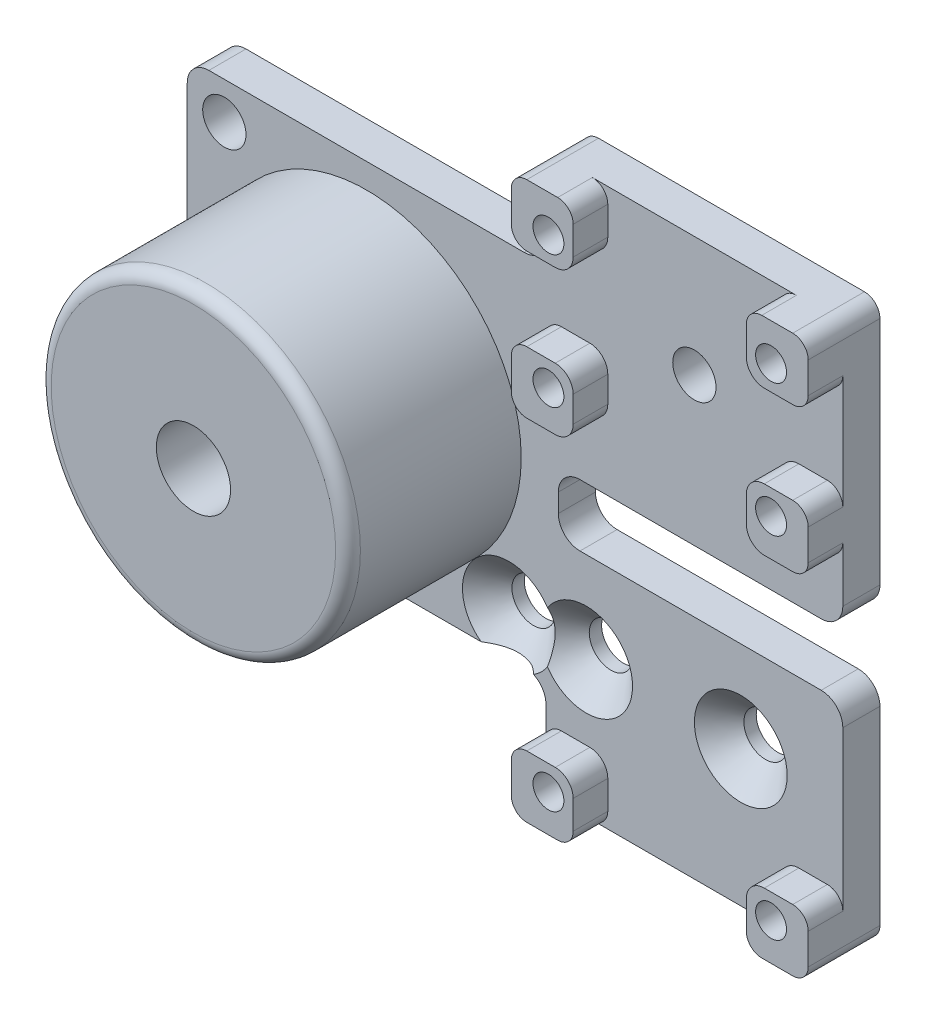
SolidWorks part; units mm, degrees
note: The reader was unsure of these and kept them because the rebuilt part matched: shared geometry of "Esquisse1<3>", "Esquisse1<5>", "Esquisse4<3>".
ref_plane "Plan de face" through (0, 0, 0) normal (0, 0, 1) x (1, 0, 0)
ref_plane "Plan de dessus" through (0, 0, 0) normal (0, 1, 0) x (1, 0, 0)
ref_plane "Plan de droite" through (0, 0, 0) normal (1, 0, 0) x (0, 0, -1)
sketch "Esquisse1" plane through (0, 0, 0) normal (0, 0, 1) x (1, 0, 0)
  line L1 (11.5, -11.5) -> (-11.5, -11.5) construction
  line L2 (11.5, -11.5) -> (11.5, 11.5) construction
  line L3 (11.5, 11.5) -> (-11.5, 11.5) construction
  line L4 (-11.5, -11.5) -> (-11.5, 11.5) construction
  line L5 (11.5, -11.5) -> (-11.5, 11.5) construction
  line L6 (11.5, 11.5) -> (-11.5, -11.5) construction
  line L13 (0, 14.5) -> (-14.5, 14.5)
  line L14 (14.5, -14.5) -> (-14.5, -14.5) construction
  line L15 (14.5, -14.5) -> (14.5, 14.5) construction
  line L16 (14.5, 14.5) -> (-14.5, 14.5) construction
  line L17 (-14.5, -14.5) -> (-14.5, 14.5) construction
  line L18 (14.5, -14.5) -> (-14.5, 14.5) construction
  line L19 (14.5, 14.5) -> (-14.5, -14.5) construction
  line L20 (-14.5, 14.5) -> (-14.5, -14.5)
  line L21 (-14.5, -14.5) -> (14.5, -14.5)
  line L22 (14.5, -14.5) -> (14.5, 0)
  circle A0 centre (0, 0) radius 10.5
  circle A2 centre (0, 0) radius 12.5
  circle A4 centre (0, 0) radius 3
  circle A5 centre (-11.5, 11.5) radius 1.75
  circle A6 centre (11.5, -11.5) radius 1.75
  circle A7 centre (-11.5, -11.5) radius 1.75
  arc A8 (0, 14.5) -> (14.5, 0) centre (0, 0) cw
  point P0 (0, 0)
  dimension "D2" = 21
  dimension "D3" = 2
  dimension "D5" = 6
  dimension "D7" = 3.5
  dimension "D1" = 23
  dimension "D6" = 29
extrude "Boss.-Extru.1" add sketch "Esquisse1" along normal blind 3
extrude "Boss.-Extru.2" add sketch "Esquisse1<3>" along normal blind 17
sketch "Esquisse1<3>" plane through (0, 0, 0) normal (0, 0, 1) x (1, 0, 0) same geometry as "Esquisse1"
extrude "Enlèv. mat.-Extru.1" cut sketch "Esquisse1<5>" along normal blind 10
sketch "Esquisse1<5>" plane through (0, 0, 0) normal (0, 0, 1) x (1, 0, 0) same geometry as "Esquisse1"
sketch "Esquisse4" plane through (0, 0, 0) normal (0, 0, -1) x (-1, 0, 0)
  line L0 (-11.5, -11.5) -> (-17.7503, -11.5) construction
  line L14 (-14.5, 22.5) -> (-14.5, -22.5)
  line L15 (-14.5, -14.5) -> (-14.5, 0) construction
  line L18 (-15.5, 0.85) -> (-38.5, 0.85)
  line L31 (-17.7503, -11.5) -> (-30.2503, -11.5) construction
  line L32 (-26.5, 12.8) -> (-26.5, 22.5) construction
  line L33 (-35.5, 8.8) -> (-35.5, 19.5) construction
  line L34 (-35.5, 8.8) -> (-35.5, -19.5) construction
  line L35 (-35.5, 19.5) -> (-38.5, 19.5) construction
  line L36 (-35.5, 19.5) -> (-35.5, 22.5) construction
  line L37 (-35.5, 8.8) -> (-38.5, 5.8) construction
  line L38 (-35.5, 8.8) -> (-33.5, 10.8) construction
  line L39 (-19.5, -22.5) -> (-19.5, -17.5)
  line L40 (-14.5, -17.5) -> (-19.5, -17.5)
  line L41 (-14.5, 5.8) -> (-19.5, 5.8)
  line L42 (-19.5, 10.8) -> (-19.5, 5.8)
  line L43 (-14.5, 10.8) -> (-19.5, 10.8)
  line L44 (-19.5, 22.5) -> (-19.5, 17.5)
  line L45 (-14.5, 17.5) -> (-19.5, 17.5)
  line L46 (0, 14.5) -> (14.5, 14.5) construction
  line L47 (0, 14.5) -> (-14.5, 14.5)
  line L48 (-17.5, 8.8) -> (-35.5, 8.8) construction
  line L49 (-26.5, 12.8) -> (-26.5, 8.8) construction
  line L51 (-33.5, 22.5) -> (-33.5, 17.5)
  line L52 (-38.5, 17.5) -> (-33.5, 17.5)
  line L53 (-33.5, 10.8) -> (-33.5, 5.8)
  line L54 (-38.5, 10.8) -> (-33.5, 10.8)
  line L55 (-38.5, 5.8) -> (-33.5, 5.8)
  line L56 (-38.5, -17.5) -> (-33.5, -17.5)
  line L57 (-33.5, -22.5) -> (-33.5, -17.5)
  line L59 (-38.5, -4.15) -> (-15.5, -4.15)
  line L60 (-15.5, 0.85) -> (-15.5, -4.15)
  line L79 (-38.5, -22.5) -> (-14.5, -22.5)
  line L83 (-38.5, 22.5) -> (-14.5, 22.5)
  line L84 (-38.5, 22.5) -> (-38.5, -22.5)
  circle A8 centre (11.5, 11.5) radius 1.75 construction
  circle A11 centre (-17.7503, -11.5) radius 1.75
  circle A12 centre (-30.2503, -11.5) radius 1.75
  circle A13 centre (-26.5, 12.8) radius 1.75
  circle A14 centre (-35.5, 19.5) radius 1.25
  circle A15 centre (-35.5, 8.8) radius 1.25
  circle A16 centre (-35.5, -19.5) radius 1.25
  circle A17 centre (-17.5, 8.8) radius 1.25
  circle A18 centre (-17.5, -19.5) radius 1.25
  circle A19 centre (-17.5, 19.5) radius 1.25
  arc A20 (-14.5, 0) -> (0, 14.5) centre (0, 0) cw
  arc A21 (0, 14.5) -> (-14.5, 0) centre (0, 0) ccw construction
  point P8 (-38.5, 0)
  dimension "D3" = 5
  dimension "D4" = 5
  dimension "D6" = 18.35
  dimension "D7" = 12.5
  dimension "D8" = 4
  dimension "D10" = 10.7
  dimension "D12" = 2.5
  dimension "D13" = 1
  dimension "D1" = 45
  dimension "D2" = 24
  dimension "D5" = 6.2503
  dimension "D9" = 28.3
  dimension "D11" = 3
extrude "Boss.-Extru.4" add sketch "Esquisse4" against normal up to surface (3 mm away)
extrude "Boss.-Extru.5" add sketch "Esquisse4<3>" against normal blind 5.8 contours L39 L79 L14 L40 A18 | L56 L84 L79 L57 A16 | L54 L84 L55 L53 A15 | L83 L84 L52 L51 A14 | L83 L44 L45 L14 A19 | L14 L43 L42 L41 A17
sketch "Esquisse4<3>" plane through (0, 0, 0) normal (0, 0, -1) x (-1, 0, 0) same geometry as "Esquisse4"
fillet "Congé4" radius 1.75 8 edges at (14.5, -14.5, 1.5) (-14.5, -14.5, 1.5) (-14.5, 14.5, 1.5) (38.5, -4.15, 1.5) (15.5, -4.15, 1.5) (15.5, 0.85, 1.5) (38.5, 0.85, 1.5) (14.5, 14.5, 1.5)
fillet "Congé5" radius 1.25 16 edges at (19.5, -22.5, 4.4) (14.5, -17.5, 4.4) (38.5, -17.5, 4.4) (33.5, -22.5, 4.4) (38.5, 10.8, 4.4) (38.5, 5.8, 4.4) (33.5, 22.5, 4.4) (38.5, 17.5, 4.4) (19.5, 22.5, 4.4) (14.5, 17.5, 4.4) (14.5, 10.8, 4.4) (14.5, 5.8, 4.4) (14.5, -22.5, 2.9) (38.5, -22.5, 2.9) (38.5, 22.5, 2.9) (14.5, 22.5, 2.9)
fillet "Congé6" radius 1.45 8 edges at (19.5, 17.5, 4.4) (33.5, 17.5, 4.4) (33.5, 5.8, 4.4) (33.5, 10.8, 4.4) (19.5, 10.8, 4.4) (19.5, 5.8, 4.4) (19.5, -17.5, 4.4) (33.5, -17.5, 4.4)
chamfer "Chanfrein2" distance 2 angle 45 3 edges at (13.25, -11.5, 3) (19.5003, -11.5, 3) (32.0003, -11.5, 3)
sketch "Esquisse5" plane through (0, 0, 0) normal (0, 0, -1) x (-1, 0, 0)
  circle A0 centre (-35.5, 19.5) radius 2.5
  circle A1 centre (-17.5, 19.5) radius 2.5
  circle A2 centre (-35.5, 8.8) radius 2.5
  circle A3 centre (-17.5, 8.8) radius 2.5
  dimension "D1" = 5
extrude "Enlèv. mat.-Extru.5" cut sketch "Esquisse5" against normal blind 2.8
fillet "Congé7" radius 1 1 edges at (12.5, 0, 17)
